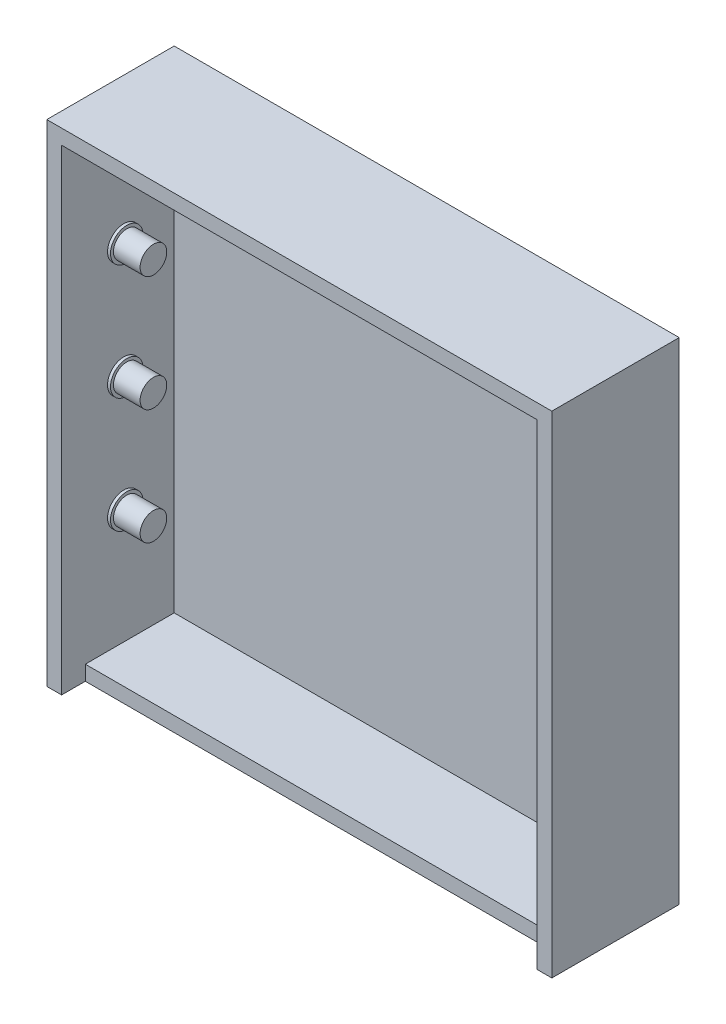
SolidWorks part; units mm, degrees
ref_plane "Front Plane" through (0, 0, 0) normal (0, 0, 1) x (1, 0, 0)
ref_plane "Top Plane" through (0, 0, 0) normal (0, 1, 0) x (1, 0, 0)
ref_plane "Right Plane" through (0, 0, 0) normal (1, 0, 0) x (0, 0, -1)
sketch "Sketch1" plane through (0, 0, 0) normal (0, 0, 1) x (1, 0, 0)
  line L1 (0, 0) -> (170.47, 0)
  line L2 (0, 0) -> (0, 165.71)
  line L3 (0, 165.71) -> (170.47, 165.71)
  line L4 (170.47, 0) -> (170.47, 165.71)
  dimension "D1" = 165.71
  dimension "D2" = 170.47
extrude "Boss-Extrude1" add sketch "Sketch1" along normal blind 5
sketch "Sketch2" plane through (0, 0, 5) normal (0, 0, 1) x (1, 0, 0)
  line L0 (0, 0) -> (0, 165.71)
  line L1 (0, 165.71) -> (170.47, 165.71)
  line L2 (170.47, 165.71) -> (170.47, 0)
  line L3 (170.47, 0) -> (0, 0)
  line L4 (5, 160.71) -> (5, 5)
  line L5 (5, 5) -> (165.47, 5)
  line L6 (165.47, 5) -> (165.47, 160.71)
  line L7 (165.47, 160.71) -> (5, 160.71)
  dimension "D1" = 5
  dimension "D2" = 5
  dimension "D3" = 5
  dimension "D4" = 5
extrude "Boss-Extrude2" add sketch "Sketch2" along normal blind 38
sketch "Sketch3" plane through (0, 0, 43) normal (0, 0, 1) x (1, 0, 0)
  line L0 (5, 5) -> (165.47, 5) construction
  line L1 (5, 5) -> (165.47, 5)
  line L2 (5, 5) -> (5, 0)
  line L3 (5, 0) -> (165.47, 0)
  line L4 (165.47, 5) -> (165.47, 0)
  line L5 (0, 0) -> (170.47, 0) construction
  line L6 (0, 165.71) -> (0, 0) construction
  dimension "D1" = 160.47
  dimension "D2" = 5
extrude "Cut-Extrude1" cut sketch "Sketch3" against normal blind 8
sketch "Sketch5" plane through (165.47, 0, 0) normal (-1, 0, 0) x (0, 0, 1)
  line L0 (43, 160.71) -> (5, 160.71) construction
  line L1 (43, 0) -> (43, 160.71) construction
  circle A0 centre (22, 121.7825) radius 5.5
  dimension "D1" = 11
  dimension "D2" = 38.9275
  dimension "D3" = 21
extrude "Boss-Extrude3" add sketch "Sketch5" along normal blind 1
sketch "Sketch6" plane through (164.47, 0, 0) normal (-1, 0, 0) x (0, 0, 1)
  circle A0 centre (22, 121.7825) radius 4.5
  dimension "D1" = 9
extrude "Boss-Extrude4" add sketch "Sketch6" along normal blind 9
ref_plane "Plane1" through (85.235, 0, 0) normal (-1, 0, 0) x (0, 0, 1)
pattern_linear "LPattern1" count 3 spacing 38.9275 along (0, -1, 0) of "Boss-Extrude4", "Boss-Extrude3"
mirror "Mirror1" about plane through (85.235, 0, 0) normal (-1, 0, 0) of "LPattern1"
